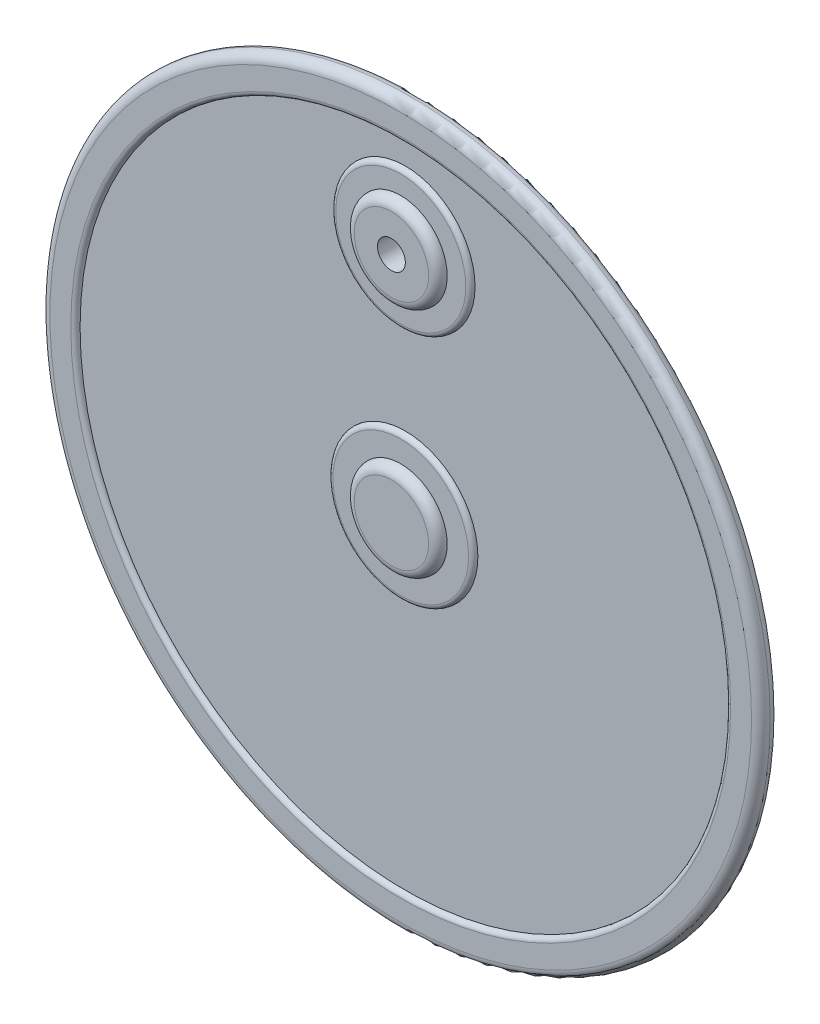
SolidWorks part; units mm, degrees
ref_plane "正面" through (0, 0, 0) normal (0, 0, 1) x (1, 0, 0)
ref_plane "平面" through (0, 0, 0) normal (0, 1, 0) x (1, 0, 0)
ref_plane "右側面" through (0, 0, 0) normal (1, 0, 0) x (0, 0, -1)
sketch "ｽｹｯﾁ3" plane through (0, 0, 0) normal (0, 0, 1) x (1, 0, 0)
  circle A0 centre (0, 0) radius 77.5
extrude "ﾎﾞｽ - 押し出し1" add sketch "ｽｹｯﾁ3" along normal blind 4
fillet "ﾌｨﾚｯﾄ1" radius 2 2 edges at (77.5, 0, 4) (77.5, 0, 0)
sketch "ｽｹｯﾁ4" plane through (0, 0, 0) normal (0, 0, -1) x (-1, 0, 0)
  circle A0 centre (0, 0) radius 69.5
  circle A1 centre (0, 0) radius 73.5
extrude "ｶｯﾄ - 押し出し1" cut sketch "ｽｹｯﾁ4" against normal blind 2
fillet "ﾌｨﾚｯﾄ2" radius 2 1 edges at (-69.5, 0, 0)
sketch "ｽｹｯﾁ6" plane through (0, 0, 0) normal (0, 0, -1) x (-1, 0, 0)
  line L0 (13, 50) -> (-13, 50) construction
  line L1 (13, 38) -> (-13, 38)
  line L2 (13, 62) -> (-13, 62)
  arc A0 (13, 38) -> (13, 62) centre (13, 50) ccw
  arc A1 (-13, 62) -> (-13, 38) centre (-13, 50) ccw
  point P2 (0, 50)
extrude "ｶｯﾄ - 押し出し2" cut sketch "ｽｹｯﾁ6" against normal blind 2
sketch "ｽｹｯﾁ7" plane through (0, 0, 2) normal (0, 0, -1) x (-1, 0, 0)
  circle A0 centre (0, 50) radius 10
extrude "ﾎﾞｽ - 押し出し2" add sketch "ｽｹｯﾁ7" along normal blind 2
sketch "ｽｹｯﾁ8" plane through (0, 0, 0) normal (0, 0, -1) x (-1, 0, 0)
  circle A0 centre (0, 50) radius 6
extrude "ﾎﾞｽ - 押し出し3" add sketch "ｽｹｯﾁ8" along normal blind 10
sketch "ｽｹｯﾁ9" plane through (0, 0, 4) normal (0, 0, 1) x (1, 0, 0)
  circle A0 centre (0, 50) radius 10
extrude "ﾎﾞｽ - 押し出し4" add sketch "ｽｹｯﾁ9" along normal blind 2
sketch "ｽｹｯﾁ10" plane through (0, 0, -10) normal (0, 0, -1) x (-1, 0, 0)
  circle A0 centre (0, 50) radius 3
extrude "ｶｯﾄ - 押し出し3" cut sketch "ｽｹｯﾁ10" against normal blind 16
fillet "ﾌｨﾚｯﾄ3" radius 2 1 edges at (10, 50, 6)
fillet "ﾌｨﾚｯﾄ4" radius 2 4 edges at (-25, 50, 0) (0, 62, 0) (0, 38, 0) (25, 50, 0)
sketch "ｽｹｯﾁ11" plane through (0, 0, 4) normal (0, 0, 1) x (1, 0, 0)
  circle A0 centre (0, 0) radius 10
extrude "ﾎﾞｽ - 押し出し5" add sketch "ｽｹｯﾁ11" along normal blind 2
fillet "ﾌｨﾚｯﾄ5" radius 2 1 edges at (10, 0, 6)
sketch "ｽｹｯﾁ12" plane through (0, 0, 4) normal (0, 0, 1) x (1, 0, 0)
  circle A0 centre (0, 0) radius 15.6064
  circle A1 centre (0, 50) radius 15
  circle A2 centre (0, 0) radius 70
extrude "ｶｯﾄ - 押し出し4" cut sketch "ｽｹｯﾁ12" against normal blind 1
fillet "ﾌｨﾚｯﾄ6" radius 1 3 edges at (15, 50, 4) (70, 0, 4) (15.6064, 0, 4)
sketch "ｽｹｯﾁ13" plane through (0, 0, 0) normal (0, 0, -1) x (-1, 0, 0)
  circle A0 centre (0, 0) radius 15
extrude "ｶｯﾄ - 押し出し5" cut sketch "ｽｹｯﾁ13" against normal blind 2
sketch "ｽｹｯﾁ14" plane through (0, 0, 2) normal (0, 0, -1) x (-1, 0, 0)
  circle A0 centre (0, 0) radius 10
extrude "ﾎﾞｽ - 押し出し6" add sketch "ｽｹｯﾁ14" along normal blind 2
fillet "ﾌｨﾚｯﾄ7" radius 2 1 edges at (-15, 0, 0)
sketch "ｽｹｯﾁ15" plane through (0, 0, 0) normal (0, 0, -1) x (-1, 0, 0)
  circle A0 centre (0, 0) radius 4
extrude "ﾎﾞｽ - 押し出し7" add sketch "ｽｹｯﾁ15" along normal blind 7
